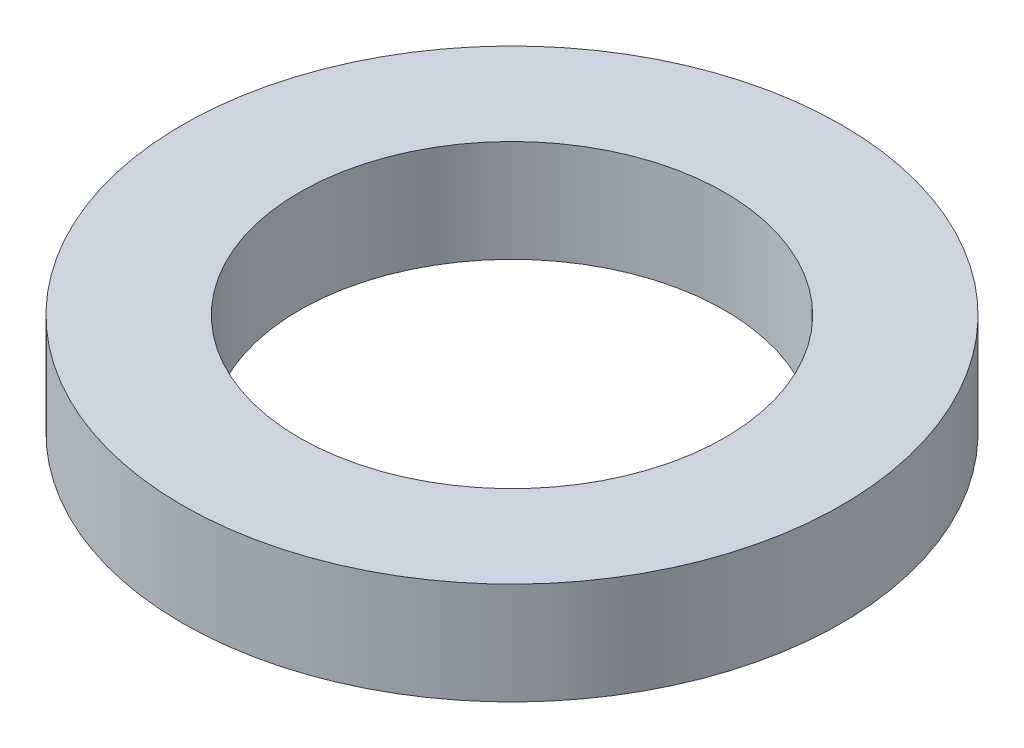
SolidWorks part; units mm, degrees
ref_plane "Front Plane" through (0, 0, 0) normal (0, 0, 1) x (1, 0, 0)
ref_plane "Top Plane" through (0, 0, 0) normal (0, 1, 0) x (1, 0, 0)
ref_plane "Right Plane" through (0, 0, 0) normal (1, 0, 0) x (0, 0, -1)
sketch "Sketch1" plane through (0, 0, 0) normal (0, 1, 0) x (1, 0, 0)
  circle A0 centre (0, 0) radius 77.5
  dimension "FLANGE_OD" = 155
extrude "Boss-Extrude1" add sketch "Sketch1" along normal blind 24
sketch "Sketch2" plane through (0, 0, 0) normal (0, 1, 0) x (1, 0, 0)
  circle A0 centre (0, 0) radius 50
  dimension "BORE_D" = 100
extrude "Cut-Extrude1" cut sketch "Sketch2" along normal through all
sketch "Sketch3" plane through (0, 24, 0) normal (0, 1, 0) x (1, 0, 0)
  circle A0 centre (0, 0) radius 28.2534 construction
  circle A1 centre (-28.2534, 0) radius 2.4432
  dimension "BOLT_D" = 4.8863
  dimension "BOLT_PCD" = 56.5067
extrude "Cut-Extrude2" cut sketch "Sketch3" against normal blind 20.6173 rebuild error yes
pattern_circular "CirPattern1" count 3 over 360 rebuild error yes
